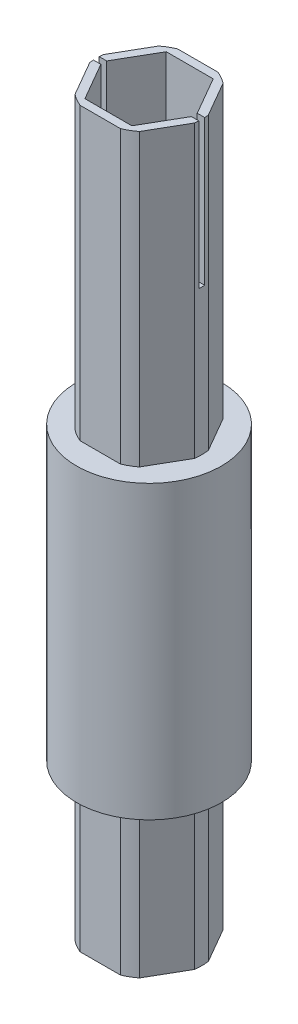
SolidWorks part; units mm, degrees
material "PET"
ref_plane "Front Plane" through (0, 0, 0) normal (0, 0, 1) x (1, 0, 0)
ref_plane "Top Plane" through (0, 0, 0) normal (0, 1, 0) x (1, 0, 0)
ref_plane "Right Plane" through (0, 0, 0) normal (1, 0, 0) x (0, 0, -1)
sketch "Sketch1" plane through (0, 0, 0) normal (0, 1, 0) x (1, 0, 0)
  line L1 (6.8647, 0.9115) -> (4.2218, 5.4893)
  line L2 (2.643, 6.4008) -> (-2.643, 6.4008)
  line L3 (-4.2218, 5.4893) -> (-6.8647, 0.9115)
  line L4 (-6.8647, -0.9115) -> (-4.2218, -5.4893)
  line L5 (-2.643, -6.4008) -> (2.643, -6.4008)
  line L6 (4.2218, -5.4893) -> (6.8647, -0.9115)
  circle A0 centre (0, 0) radius 6.4008 construction
  arc A1 (-2.643, 6.4008) -> (-4.2218, 5.4893) centre (0, 0) ccw
  arc A2 (4.2218, 5.4893) -> (2.643, 6.4008) centre (0, 0) ccw
  arc A3 (6.8647, -0.9115) -> (6.8647, 0.9115) centre (0, 0) ccw
  arc A4 (2.643, -6.4008) -> (4.2218, -5.4893) centre (0, 0) ccw
  arc A5 (-4.2218, -5.4893) -> (-2.643, -6.4008) centre (0, 0) ccw
  arc A6 (-6.8647, 0.9115) -> (-6.8647, -0.9115) centre (0, 0) ccw
  dimension "D1" = 12.8016
  dimension "D2" = 13.85
extrude "Boss-Extrude1" add sketch "Sketch1" against normal blind 19.812
sketch "Sketch2" plane through (0, 0, 0) normal (0, -1, 0) x (-1, 0, 0)
  circle A0 centre (0, 0) radius 9.5
  dimension "D1" = 19
extrude "Boss-Extrude2" add sketch "Sketch2" against normal blind 38.227
extrude "Boss-Extrude6" add sketch "Sketch1<4>" along normal blind 76.327
sketch "Sketch1<4>" plane through (0, 0, 0) normal (0, 1, 0) x (1, 0, 0) same geometry as "Sketch1"
sketch "Sketch6" plane through (0, 76.327, 0) normal (0, 1, 0) x (1, 0, 0)
  line L1 (-6.925, 0.381) -> (6.925, 0.381)
  line L2 (-6.925, 0.381) -> (-6.925, -0.381)
  line L3 (-6.925, -0.381) -> (6.925, -0.381)
  line L4 (6.925, 0.381) -> (6.925, -0.381)
  line L5 (-6.925, 0.381) -> (6.925, -0.381) construction
  line L6 (-6.925, -0.381) -> (6.925, 0.381) construction
  arc A0 (6.8647, -0.9115) -> (6.8647, 0.9115) centre (0, 0) ccw construction
  point P0 (0, 0)
  dimension "D1" = 0.762
extrude "Cut-Extrude1" cut sketch "Sketch6" against normal blind 19.05
sketch "Sketch7" plane through (0, 76.327, 0) normal (0, 1, 0) x (1, 0, 0)
  line L1 (4.0415, 0) -> (2.0207, 3.5) construction
  line L2 (2.0207, 3.5) -> (-2.0207, 3.5) construction
  line L3 (-2.0207, 3.5) -> (-4.0415, 0) construction
  line L4 (-4.0415, 0) -> (-2.0207, -3.5) construction
  line L5 (-2.0207, -3.5) -> (2.0207, -3.5) construction
  line L6 (2.0207, -3.5) -> (4.0415, 0) construction
  line L8 (3.0796, 5.334) -> (-3.0796, 5.334)
  line L9 (-3.0796, 5.334) -> (-6.1592, 0)
  line L10 (-6.1592, 0) -> (-3.0796, -5.334)
  line L11 (-3.0796, -5.334) -> (3.0796, -5.334)
  line L12 (3.0796, -5.334) -> (6.1592, 0)
  line L13 (6.1592, 0) -> (3.0796, 5.334)
  circle A0 centre (0, 0) radius 3.5 construction
  circle A1 centre (0, 0) radius 5.334 construction
  dimension "D1" = 7
  dimension "D2" = 10.668
extrude "Cut-Extrude2" cut sketch "Sketch7" against normal blind 29.017
